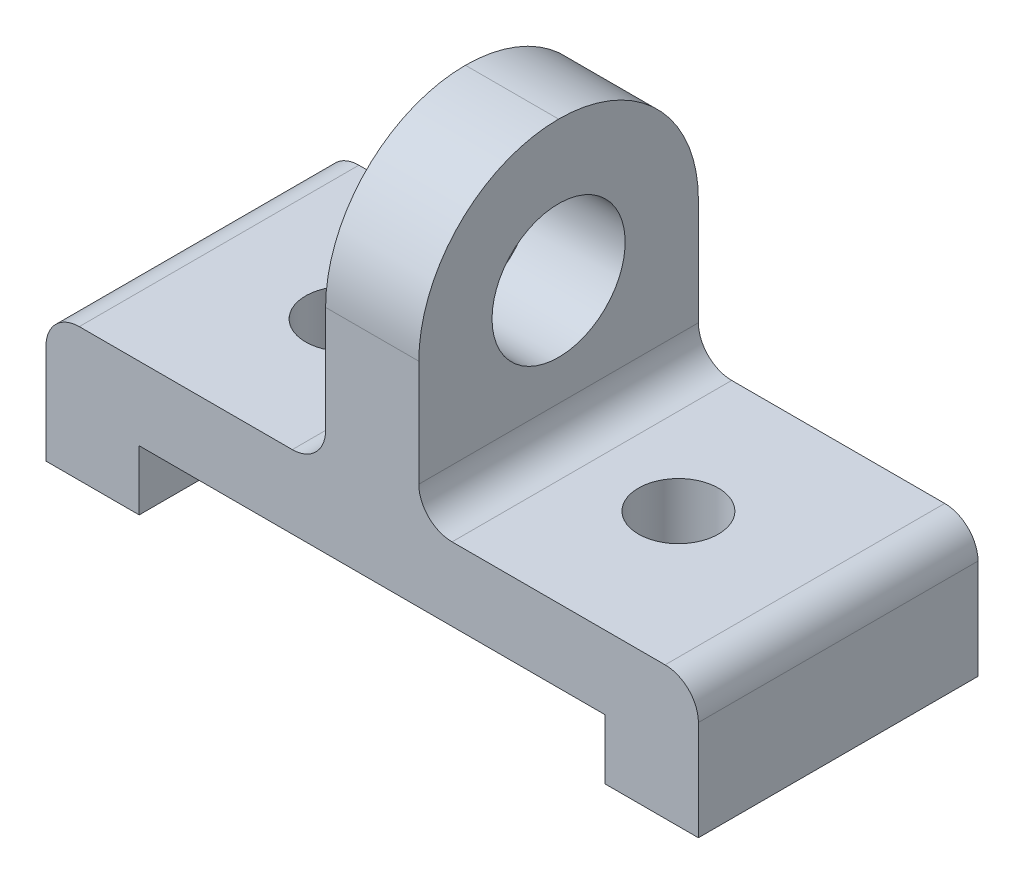
SolidWorks part; units mm, degrees
ref_plane "Front Plane" through (0, 0, 0) normal (0, 0, 1) x (1, 0, 0)
ref_plane "Top Plane" through (0, 0, 0) normal (0, 1, 0) x (1, 0, 0)
ref_plane "Right Plane" through (0, 0, 0) normal (1, 0, 0) x (0, 0, -1)
sketch "Sketch2" plane through (0, 0, 0) normal (0, 1, 0) x (1, 0, 0)
  line L1 (-49, 21) -> (49, 21)
  line L2 (-49, 21) -> (-49, -21)
  line L3 (-49, -21) -> (49, -21)
  line L4 (49, 21) -> (49, -21)
  line L5 (-49, 21) -> (49, -21) construction
  line L6 (-49, -21) -> (49, 21) construction
  point P0 (0, 0)
  dimension "D1" = 98
  dimension "D2" = 42
extrude "Boss-Extrude1" add sketch "Sketch2" along normal blind 11
sketch "Sketch3" plane through (0, 0, 0) normal (0, 1, 0) x (1, 0, 0)
  line L0 (-49, -21) -> (49, -21) construction
  line L1 (49, 21) -> (35, 21)
  line L2 (49, 21) -> (49, -21)
  line L3 (49, -21) -> (35, -21)
  line L4 (35, 21) -> (35, -21)
  line L5 (49, 21) -> (-49, 21) construction
  line L6 (-49, -21) -> (-35, -21)
  line L7 (-49, -21) -> (-49, 21)
  line L8 (-49, 21) -> (-35, 21)
  line L9 (-35, -21) -> (-35, 21)
  dimension "D1" = 14
  dimension "D2" = 14
extrude "Boss-Extrude2" add sketch "Sketch3" against normal blind 9
fillet "Fillet1" radius 5 2 edges at (49, 11, 0) (-49, 11, 0)
sketch "Sketch4" plane through (0, 0, 0) normal (0, 1, 0) x (1, 0, 0)
  line L0 (0, 0) -> (25, 0) construction
  line L1 (0, 0) -> (-25, 0) construction
  circle A0 centre (-25, 0) radius 6
  circle A1 centre (25, 0) radius 6
  dimension "D3" = 12
  dimension "D4" = 12
  dimension "D1" = 25
  dimension "D2" = 25
extrude "Cut-Extrude1" cut sketch "Sketch4" against normal through all both and the other way through all
sketch "Sketch5" plane through (0, 0, 0) normal (0, 1, 0) x (1, 0, 0)
  line L0 (0, 0) -> (0, -21) construction
  line L1 (-44, -21) -> (44, -21) construction
  line L2 (0, 0) -> (0, 21) construction
  line L3 (44, 21) -> (-44, 21) construction
  line L5 (-7, 21) -> (7, 21)
  line L6 (-7, 21) -> (-7, -21)
  line L7 (-7, -21) -> (7, -21)
  line L8 (7, 21) -> (7, -21)
  line L9 (-7, 21) -> (7, -21) construction
  line L10 (-7, -21) -> (7, 21) construction
  dimension "D1" = 14
extrude "Boss-Extrude4" add sketch "Sketch5" along normal blind 53
fillet "Fillet2" radius 21 2 edges at (0, 53, -21) (0, 53, 21)
fillet "Fillet3" radius 5 2 edges at (-7, 11, 0) (7, 11, 0)
sketch "Sketch6" plane through (0, 0, 0) normal (1, 0, 0) x (0, 0, -1)
  circle A0 centre (0, 32) radius 10
  dimension "D1" = 20
extrude "Cut-Extrude2" cut sketch "Sketch6" along normal through all both and the other way through all
